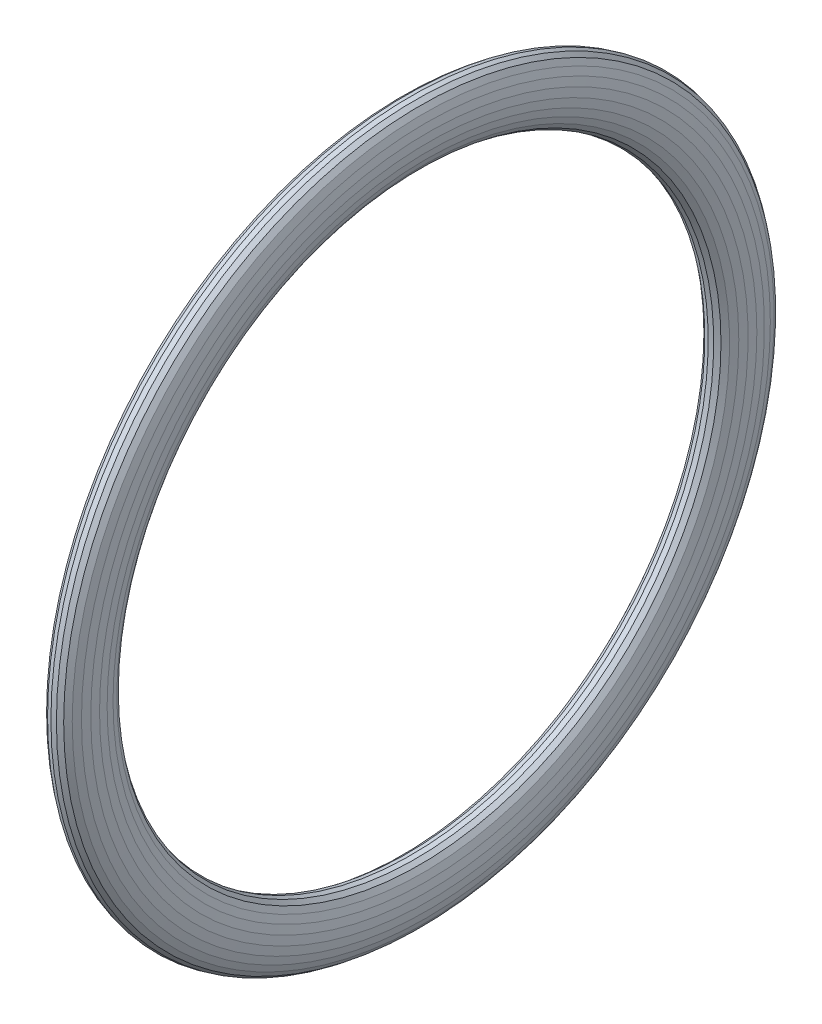
SolidWorks part; units mm, degrees
ref_plane "Front Plane" through (0, 0, 0) normal (0, 0, 1) x (1, 0, 0)
ref_plane "Top Plane" through (0, 0, 0) normal (0, 1, 0) x (1, 0, 0)
ref_plane "Right Plane" through (0, 0, 0) normal (1, 0, 0) x (0, 0, -1)
sketch "O_Ring_Pintle Sketch" plane through (0, 0, 0) normal (0, 0, 1) x (1, 0, 0)
  line L0 (-1000, 0) -> (1000, 0) construction
  line L1 (-1.295, 12.4) -> (-1.273, 12.708)
  line L2 (-1.273, 12.708) -> (-1.2086, 12.995)
  line L3 (-1.2086, 12.995) -> (-1.1061, 13.2415)
  line L4 (-1.1061, 13.2415) -> (-0.9725, 13.4306)
  line L5 (-0.9725, 13.4306) -> (-0.8169, 13.5495)
  line L6 (-0.8169, 13.5495) -> (-0.65, 13.59)
  line L7 (-0.65, 13.59) -> (-0.4831, 13.5495)
  line L8 (-0.4831, 13.5495) -> (-0.3275, 13.4306)
  line L9 (-0.3275, 13.4306) -> (-0.1939, 13.2415)
  line L10 (-0.1939, 13.2415) -> (-0.0914, 12.995)
  line L11 (-0.0914, 12.995) -> (-0.027, 12.708)
  line L12 (-0.027, 12.708) -> (-0.005, 12.4)
  line L13 (-0.005, 12.4) -> (-0.027, 12.092)
  line L14 (-0.027, 12.092) -> (-0.0914, 11.805)
  line L15 (-0.0914, 11.805) -> (-0.1939, 11.5585)
  line L16 (-0.1939, 11.5585) -> (-0.3275, 11.3694)
  line L17 (-0.3275, 11.3694) -> (-0.4831, 11.2505)
  line L18 (-0.4831, 11.2505) -> (-0.65, 11.21)
  line L19 (-0.65, 11.21) -> (-0.8169, 11.2505)
  line L20 (-0.8169, 11.2505) -> (-0.9725, 11.3694)
  line L21 (-0.9725, 11.3694) -> (-1.1061, 11.5585)
  line L22 (-1.1061, 11.5585) -> (-1.2086, 11.805)
  line L23 (-1.2086, 11.805) -> (-1.273, 12.092)
  line L24 (-1.273, 12.092) -> (-1.295, 12.4)
revolve "O_Ring_Pintle" add sketch "O_Ring_Pintle Sketch" angle 360 about L0
ref_axis "Engine Axis" through (0.0595, 0, 0) along (-1, 0, 0)
